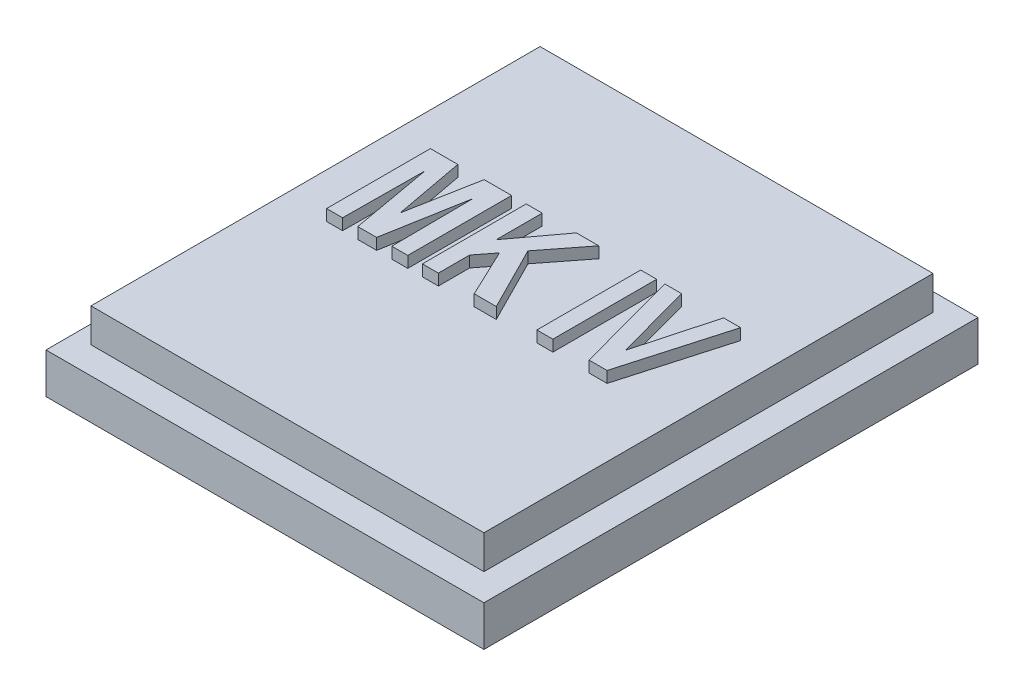
SolidWorks part; units mm, degrees
ref_plane "Спереди" through (0, 0, 0) normal (0, 0, 1) x (1, 0, 0)
ref_plane "Сверху" through (0, 0, 0) normal (0, 1, 0) x (1, 0, 0)
ref_plane "Справа" through (0, 0, 0) normal (1, 0, 0) x (0, 0, -1)
sketch "Sketch1" plane through (0, 0, 0) normal (0, 1, 0) x (1, 0, 0)
  line L1 (13.8, -14.8) -> (-13.8, -14.8)
  line L2 (13.8, -14.8) -> (13.8, 14.8)
  line L3 (13.8, 14.8) -> (-13.8, 14.8)
  line L4 (-13.8, -14.8) -> (-13.8, 14.8)
  line L5 (13.8, -14.8) -> (-13.8, 14.8) construction
  line L6 (13.8, 14.8) -> (-13.8, -14.8) construction
  point P0 (0, 0)
  dimension "D1" = 27.6
  dimension "D2" = 29.6
extrude "Boss-Extrude1" add sketch "Sketch1" along normal blind 4
sketch "Sketch2" plane through (0, 4, 0) normal (0, 1, 0) x (1, 0, 0)
  line L0 (-1.2, 14.8) -> (-1.2, -14.8) construction
  line L1 (13.8, 14.8) -> (-13.8, 14.8) construction
  line L2 (-13.8, -14.8) -> (13.8, -14.8) construction
  line L3 (-13.8, 3.2) -> (13.8, 3.2) construction
  line L4 (-13.8, 14.8) -> (-13.8, -14.8) construction
  line L5 (13.8, -14.8) -> (13.8, 14.8) construction
  line L7 (16.3, -16.8) -> (-18.7, -16.8)
  line L8 (16.3, -16.8) -> (16.3, 23.2)
  line L9 (16.3, 23.2) -> (-18.7, 23.2)
  line L10 (-18.7, -16.8) -> (-18.7, 23.2)
  line L11 (16.3, -16.8) -> (-18.7, 23.2) construction
  line L12 (16.3, 23.2) -> (-18.7, -16.8) construction
  point P12 (-1.2, 3.2)
  dimension "D1" = 35
  dimension "D2" = 40
  dimension "D3" = 18
  dimension "D4" = 15
extrude "Boss-Extrude2" add sketch "Sketch2" along normal blind 3
chamfer "Chamfer1" distance 0.4 angle 70 4 edges at (0, 0, 14.8) (13.8, 0, 0) (0, 0, -14.8) (-13.8, 0, 0) first distance on face at (0, 0, 0)
sketch "Sketch3" plane through (0, 7, 0) normal (0, 1, 0) x (1, 0, 0)
  line L0 (-18.7, 0.2) -> (16.3, 0.2) construction
  line L1 (-18.7, 23.2) -> (-18.7, -16.8) construction
  line L2 (16.3, -16.8) -> (16.3, 23.2) construction
  line L3 (-18.7, -16.8) -> (16.3, -16.8) construction
  text T0 "<b>MK IV</b>" font "Arial" height in points 36
  dimension "D1" = 17
extrude "Boss-Extrude3" add sketch "Sketch3" along normal blind 1
sketch "Sketch4" plane through (0, 0, 0) normal (0, -1, 0) x (1, 0, 0)
  line L0 (-18.7, 16.8) -> (16.3, 16.8) construction
  line L1 (-20.7, 18.8) -> (18.3, 18.8)
  line L2 (-20.7, 18.8) -> (-20.7, -25.2)
  line L3 (-20.7, -25.2) -> (18.3, -25.2)
  line L4 (18.3, 18.8) -> (18.3, -25.2)
  line L5 (-20.7, 18.8) -> (18.3, -25.2) construction
  line L6 (-20.7, -25.2) -> (18.3, 18.8) construction
  line L7 (-16.7, 15.3) -> (14.3, 15.3)
  line L8 (-16.7, 15.3) -> (-16.7, -21.7)
  line L9 (-16.7, -21.7) -> (14.3, -21.7)
  line L10 (14.3, 15.3) -> (14.3, -21.7)
  line L11 (-16.7, 15.3) -> (14.3, -21.7) construction
  line L12 (-16.7, -21.7) -> (14.3, 15.3) construction
  line L13 (16.3, 16.8) -> (16.3, -23.2) construction
  line L14 (16.3, -23.2) -> (-18.7, -23.2) construction
  line L15 (-18.7, -23.2) -> (-18.7, 16.8) construction
  point P0 (-1.2, -3.2)
  point P5 (-1.2, -3.2)
  dimension "D1" = 2
  dimension "D2" = 1.5
  dimension "D3" = 2
  dimension "D4" = 2
  dimension "D5" = 2
  dimension "D6" = 1.5
  dimension "D7" = 2
extrude "Boss-Extrude4" add sketch "Sketch4" against normal offset from surface (3.6 mm away) 0.4 up to face at (-1.2, 4, -3.2)
